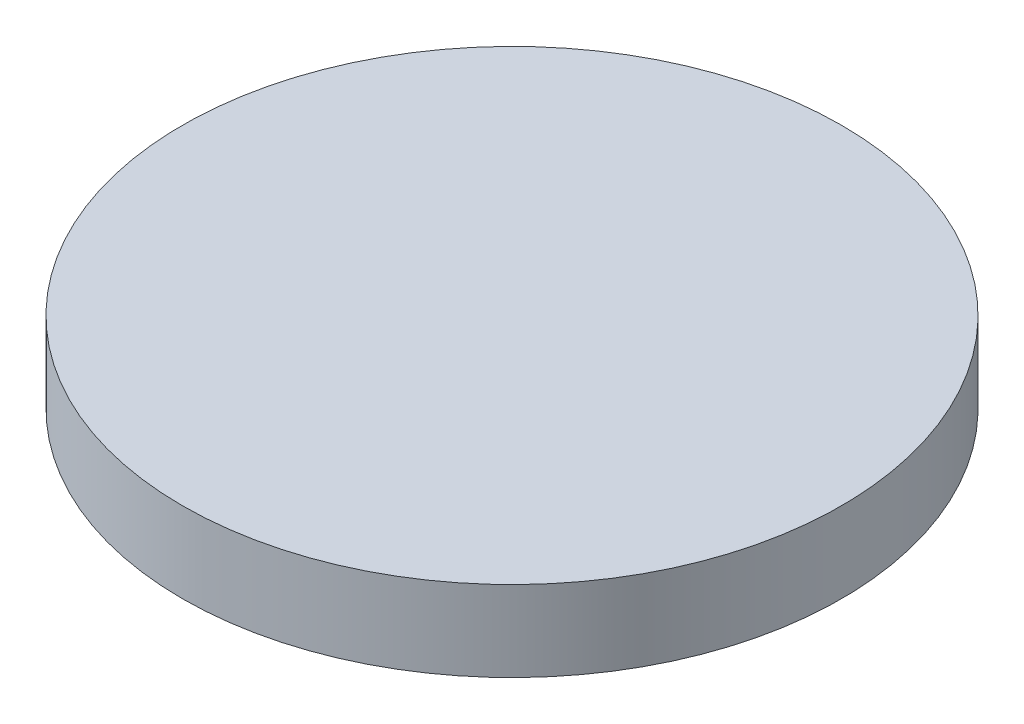
SolidWorks part; units mm, degrees
material "Сталь 3 ГОСТ 535-88"
ref_plane "Спереди" through (0, 0, 0) normal (0, 0, 1) x (1, 0, 0)
ref_plane "Сверху" through (0, 0, 0) normal (0, 1, 0) x (1, 0, 0)
ref_plane "Справа" through (0, 0, 0) normal (1, 0, 0) x (0, 0, -1)
sketch "Эскиз1" plane through (0, 0, 0) normal (0, 1, 0) x (1, 0, 0)
  circle A0 centre (0, 0) radius 45
  dimension "D1" = 90
extrude "Бобышка-Вытянуть1" add sketch "Эскиз1" along normal blind 6
sketch "Эскиз2" plane through (0, 0, 0) normal (0, -1, 0) x (1, 0, 0)
  circle A0 centre (0, 0) radius 45 construction
  circle A1 centre (0, 0) radius 45
  circle A2 centre (0, 0) radius 40
  dimension "D1" = 5
extrude "Бобышка-Вытянуть2" add sketch "Эскиз2" along normal blind 5
